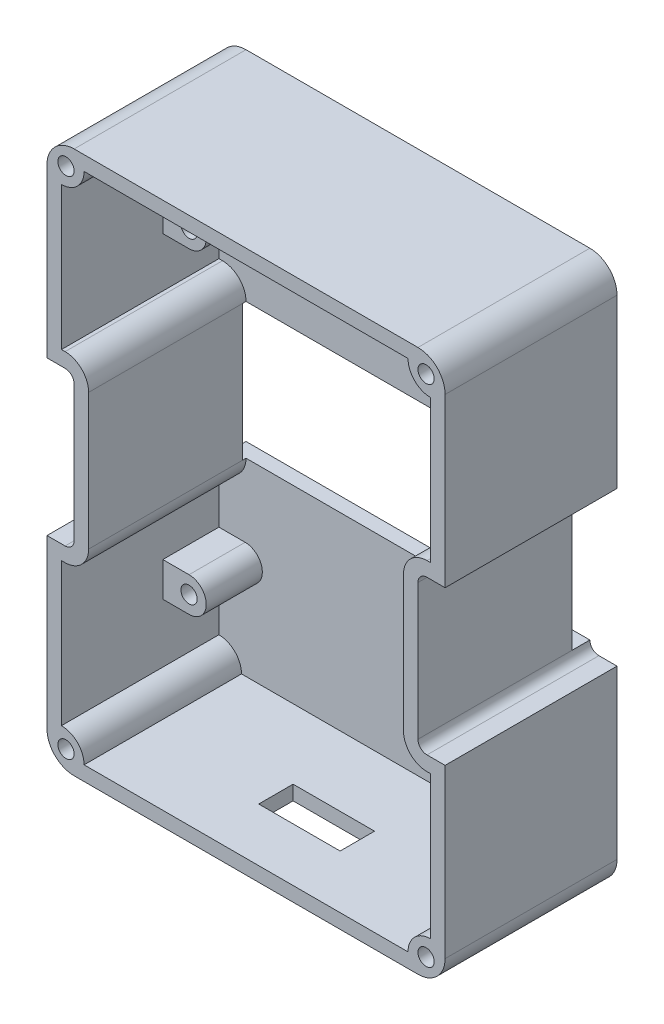
SolidWorks part; units mm, degrees
ref_plane "前视基准面" through (0, 0, 0) normal (0, 0, 1) x (1, 0, 0)
ref_plane "上视基准面" through (0, 0, 0) normal (0, 1, 0) x (1, 0, 0)
ref_plane "右视基准面" through (0, 0, 0) normal (1, 0, 0) x (0, 0, -1)
sketch "草图1" plane through (0, 0, 0) normal (0, 0, 1) x (1, 0, 0)
  line L1 (-22, -30) -> (22, -30)
  line L2 (-22, -30) -> (-22, 30)
  line L3 (-22, 30) -> (22, 30)
  line L4 (22, -30) -> (22, 30)
  line L5 (-22, -30) -> (22, 30) construction
  line L6 (-22, 30) -> (22, -30) construction
  point P0 (0, 0)
  dimension "D1" = 60
  dimension "D2" = 44
extrude "凸台-拉伸1" add sketch "草图1" along normal blind 19
sketch "草图2" plane through (0, 0, 19) normal (0, 0, 1) x (1, 0, 0)
  line L0 (-22, 30) -> (-22, -30) construction
  line L1 (-22, -8.5) -> (-19, -8.5)
  line L2 (-22, -8.5) -> (-22, 8.5)
  line L3 (-22, 8.5) -> (-19, 8.5)
  line L4 (-19, -8.5) -> (-19, 8.5)
  line L5 (-22, -30) -> (22, -30) construction
  line L6 (0, -10.45) -> (0, 10.45) construction
  line L7 (22, 8.5) -> (19, 8.5)
  line L8 (19, -8.5) -> (19, 8.5)
  line L9 (22, -8.5) -> (19, -8.5)
  line L10 (22, -8.5) -> (22, 8.5)
  point P8 (-19, 0)
  dimension "D1" = 21.5
  dimension "D2" = 3
extrude "切除-拉伸1" cut sketch "草图2" against normal through all
fillet "圆角1" radius 3 4 edges at (-22, 30, 9.5) (22, 30, 9.5) (22, -30, 9.5) (-22, -30, 9.5)
fillet "圆角2" radius 1 4 edges at (-19, 8.5, 9.5) (-19, -8.5, 9.5) (19, -8.5, 9.5) (19, 8.5, 9.5)
shell "抽壳1" thickness 1.6 removed face at (0, 0, 19)
sketch "草图3" plane through (0, 0, 1.6) normal (0, 0, 1) x (1, 0, 0)
  line L2 (-20.4, 28.4) -> (-17.9, 28.4)
  line L3 (-20.4, 28.4) -> (-20.4, 25.9)
  line L6 (-20.4, 27) -> (-20.4, 10.1) construction
  line L7 (19, 28.4) -> (-19, 28.4) construction
  arc A0 (-20.4, 25.9) -> (-17.9, 28.4) centre (-20.4, 28.4) ccw
  circle A1 centre (-19.9, 27.9) radius 0.9
  dimension "D1" = 2.5
  dimension "D2" = 1.8
  dimension "D3" = 0.5
  dimension "D4" = 0.5
extrude "凸台-拉伸2" add sketch "草图3" along normal up to surface (17.4 mm away) contours A0 L2 L3 up to face at (0, 0, 19)
extrude "切除-拉伸2" cut sketch "草图3<3>" along normal up to surface (17.4 mm away) contours A1 up to face at (0.0954, -0.0954, 19)
sketch "草图3<3>" plane through (0, 0, 1.6) normal (0, 0, 1) x (1, 0, 0) same geometry as "草图3"
mirror "镜向1" about plane through (0, 0, 0) normal (1, 0, 0) of "切除-拉伸2", "凸台-拉伸2"
mirror "镜向2" about plane through (0, 0, 0) normal (0, 1, 0) of "切除-拉伸2", "镜向1", "凸台-拉伸2"
sketch "草图4" plane through (0, 0, 1.6) normal (0, 0, 1) x (1, 0, 0)
  line L0 (22, -27) -> (22, -8.5) construction
  line L1 (20.4, -28.4) -> (13.6, -28.4)
  line L2 (20.4, -28.4) -> (20.4, -13.4)
  line L3 (20.4, -13.4) -> (13.6, -13.4)
  line L4 (13.6, -28.4) -> (13.6, -13.4)
  line L5 (15.2, -25.3) -> (17.2, -25.3)
  line L6 (15.2, -25.3) -> (15.2, -27)
  line L7 (15.2, -27) -> (17.2, -27)
  line L8 (17.2, -25.3) -> (17.2, -27)
  line L9 (-19, -30) -> (19, -30) construction
  line L10 (-19, -30) -> (19, -30) construction
  line L11 (15.2, -22.76) -> (15.2, -24.46)
  line L12 (15.2, -22.76) -> (17.2, -22.76)
  line L13 (17.2, -22.76) -> (17.2, -24.46)
  line L14 (15.2, -24.46) -> (17.2, -24.46)
  line L15 (15.2, -20.22) -> (15.2, -21.92)
  line L16 (15.2, -20.22) -> (17.2, -20.22)
  line L17 (17.2, -20.22) -> (17.2, -21.92)
  line L18 (15.2, -21.92) -> (17.2, -21.92)
  line L19 (15.2, -17.68) -> (15.2, -19.38)
  line L20 (15.2, -17.68) -> (17.2, -17.68)
  line L21 (17.2, -17.68) -> (17.2, -19.38)
  line L22 (15.2, -19.38) -> (17.2, -19.38)
  line L23 (15.2, -15.14) -> (15.2, -16.84)
  line L24 (15.2, -15.14) -> (17.2, -15.14)
  line L25 (17.2, -15.14) -> (17.2, -16.84)
  line L26 (15.2, -16.84) -> (17.2, -16.84)
  line L27 (-17.9, -28.4) -> (17.9, -28.4) construction
  line L28 (20.4, -25.9) -> (20.4, -10.1) construction
  point P32 (16.2, -15.14)
  point P33 (17, -13.4)
  point P36 (0, 0)
  dimension "D1" = 4.8
  dimension "D2" = 6.8
  dimension "D3" = 3
  dimension "D4" = 4.7
  dimension "D6" = 1.6
  dimension "D7" = 2.54
  dimension "D8" = 15
  dimension "D5" = 5
extrude "凸台-拉伸3" add sketch "草图4" along normal offset from surface (6.2 mm away) 7.8 contours L2 L3 L4 L1 up to face at (0, 0, 0)
extrude "切除-拉伸3" cut sketch "草图4<4>" against normal through all both and the other way through all contours L26 L25 L24 L23 | L22 L21 L20 L19 | L18 L17 L16 L15 | L14 L13 L12 L11 | L7 L8 L5 L6
sketch "草图4<4>" plane through (0, 0, 1.6) normal (0, 0, 1) x (1, 0, 0) same geometry as "草图4"
sketch "草图5" plane through (0, 0, 1.6) normal (0, 0, 1) x (1, 0, 0)
  line L1 (-17.5, 19.4) -> (-20.4, 19.4)
  line L2 (-20.4, 25.9) -> (-20.4, 10.1) construction
  line L3 (-20.4, 19.4) -> (-20.4, 15.6)
  line L4 (-20.4, 15.6) -> (-17.5, 15.6)
  line L5 (0, -10.45) -> (0, 10.45) construction
  line L6 (20.4, 15.6) -> (17.5, 15.6)
  line L7 (20.4, 19.4) -> (20.4, 15.6)
  line L8 (17.5, 19.4) -> (20.4, 19.4)
  line L9 (10.45, 0) -> (-10.45, 0) construction
  line L10 (-20.4, -15.6) -> (-17.5, -15.6)
  line L11 (-20.4, -19.4) -> (-20.4, -15.6)
  line L12 (-17.5, -19.4) -> (-20.4, -19.4)
  circle A0 centre (-17.5, 17.5) radius 0.9
  arc A2 (-17.5, 15.6) -> (-17.5, 19.4) centre (-17.5, 17.5) ccw
  circle A3 centre (17.5, 17.5) radius 0.9
  arc A4 (17.5, 15.6) -> (17.5, 19.4) centre (17.5, 17.5) cw
  circle A5 centre (-17.5, -17.5) radius 0.9
  arc A6 (-17.5, -15.6) -> (-17.5, -19.4) centre (-17.5, -17.5) cw
  dimension "D1" = 1.8
  dimension "D2" = 3.8
  dimension "D3" = 35
  dimension "D4" = 35
extrude "凸台-拉伸4" add sketch "草图5" along normal up to surface (6.2 mm away) up to face at (16.2, -15.99, 7.8)
sketch "草图6" plane through (0, -28.4, 0) normal (0, 1, 0) x (1, 0, 0)
  line L0 (13.6, -7.8) -> (17.9, -7.8) construction
  line L3 (-4.5, -13.1) -> (4.5, -13.1)
  line L4 (-4.5, -13.1) -> (-4.5, -9.3)
  line L5 (-4.5, -9.3) -> (4.5, -9.3)
  line L6 (4.5, -13.1) -> (4.5, -9.3)
  point P4 (0, -13.1)
  dimension "D1" = 9
  dimension "D2" = 3.8
  dimension "D3" = 1.5
extrude "切除-拉伸4" cut sketch "草图6" against normal through all
sketch "草图7" plane through (0, 0, 0) normal (0, 0, -1) x (-1, 0, 0)
  line L0 (-19, 7.5) -> (-19, -7.5) construction
  line L1 (-19, -7.5) -> (19, -7.5)
  line L2 (-19, -7.5) -> (-19, 7.5)
  line L3 (-19, 7.5) -> (19, 7.5)
  line L4 (19, -7.5) -> (19, 7.5)
  line L5 (19, -7.5) -> (19, 7.5) construction
  point P8 (0, 0)
  point P10 (0, 0)
extrude "切除-拉伸5" cut sketch "草图7" against normal blind 2
